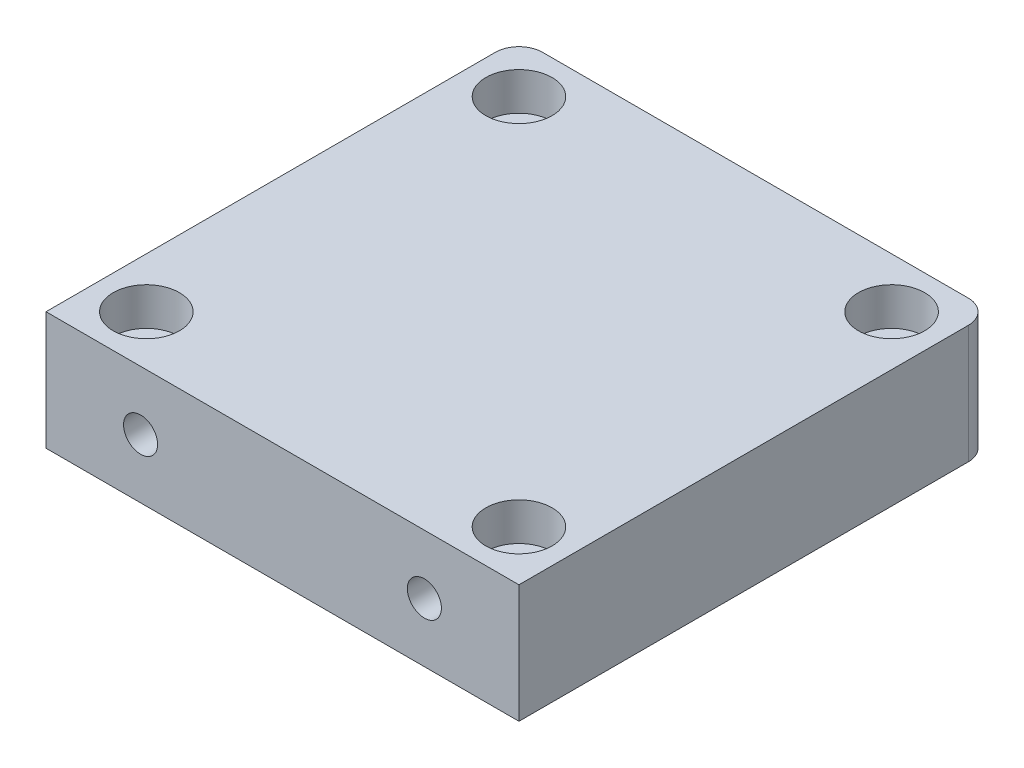
SolidWorks part; units mm, degrees
ref_plane "Front Plane" through (0, 0, 0) normal (0, 0, 1) x (1, 0, 0)
ref_plane "Top Plane" through (0, 0, 0) normal (0, 1, 0) x (1, 0, 0)
ref_plane "Right Plane" through (0, 0, 0) normal (1, 0, 0) x (0, 0, -1)
sketch "Sketch1" plane through (0, 0, 0) normal (0, 1, 0) x (1, 0, 0)
  line L0 (100, 100) -> (0, 0)
  line L1 (0, 0) -> (100, 0)
  line L2 (0, 0) -> (0, 100)
  line L3 (0, 100) -> (100, 100)
  line L4 (100, 0) -> (100, 100)
  line L5 (100, 0) -> (0, 100)
  circle A0 centre (10.6066, 89.3934) radius 4
  circle A1 centre (89.3934, 89.3934) radius 4
  circle A2 centre (89.3934, 10.6066) radius 4
  circle A3 centre (10.6066, 10.6066) radius 4
  circle A4 centre (10.6066, 89.3934) radius 7
  circle A5 centre (89.3934, 89.3934) radius 7
  circle A6 centre (10.6066, 10.6066) radius 7
  circle A7 centre (89.3934, 10.6066) radius 7
  dimension "D3" = 8
  dimension "D8" = 14
  dimension "D1" = 100
  dimension "D2" = 100
  dimension "D4" = 15
  dimension "D5" = 15
  dimension "D6" = 15
  dimension "D7" = 15
extrude "Boss-Extrude1" add sketch "Sketch1" along normal blind 25 contours A3 L0 L1 L5 A2 | A3 L0 L5 A0 L2 | A1 L0 L3 L5 A0 | A2 L5 L4 L0 A1 | L5 A4 A0 | L5 A4 A0 | L5 A7 A2 | L5 A7 A2 | L0 A5 A1 | L0 A5 A1 | L0 A6 A3 | L0 A6 A3 region at (82.7979, 0, -50) region at (50, 0, -82.7979) region at (95.7044, 0, -92.0075) region at (93.163, 0, -93.402) region at (17.2021, 0, -50) region at (50, 0, -17.2021) region at (13.2207, 0, -95.7044) region at (6.598, 0, -93.163) region at (84.5631, 0, -5.7764) region at (93.402, 0, -6.837) region at (5.7764, 0, -15.4369) region at (6.837, 0, -6.598)
sketch "Sketch2" plane through (0, 0, 0) normal (0, 0, 1) x (1, 0, 0)
  line L0 (100, 12.5) -> (0, 12.5) construction
  line L1 (100, 25) -> (100, 0) construction
  line L2 (0, 25) -> (0, 0) construction
  circle A0 centre (20, 12.5) radius 3.6
  circle A1 centre (80, 12.5) radius 3.6
  dimension "D1" = 7.2
  dimension "D2" = 20
  dimension "D3" = 20
extrude "Cut-Extrude1" cut sketch "Sketch2" against normal blind 20 contours A0 | A1
fillet "Fillet1" radius 5 2 edges at (100, 12.5, -100) (0, 12.5, -100)
extrude "Cut-Extrude3" cut sketch "Sketch1<3>" along normal up to surface (25 mm away) from offset 17 contours A6 | A4 | A5 | A7 up to face at (10.6066, 25, -85.3934)
sketch "Sketch1<3>" plane through (0, 0, 0) normal (0, 1, 0) x (1, 0, 0) same geometry as "Sketch1"
